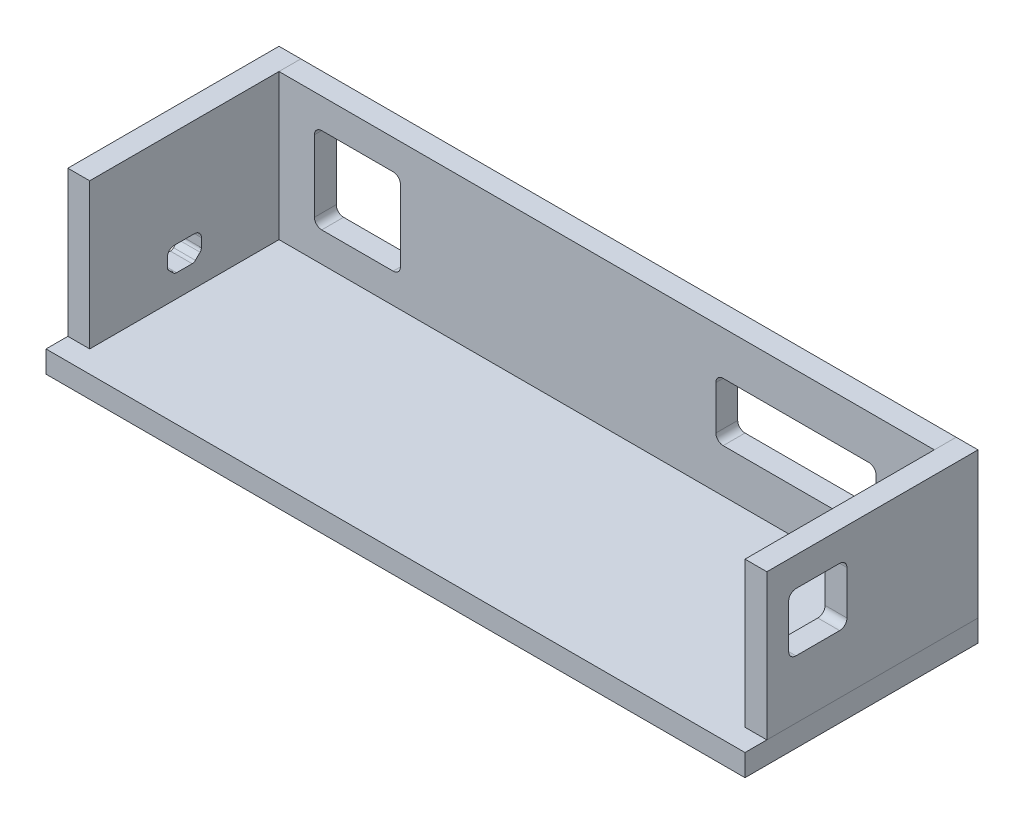
SolidWorks part; units mm, degrees
ref_plane "Front Plane" through (0, 0, 0) normal (0, 0, 1) x (1, 0, 0)
ref_plane "Top Plane" through (0, 0, 0) normal (0, 1, 0) x (1, 0, 0)
ref_plane "Right Plane" through (0, 0, 0) normal (1, 0, 0) x (0, 0, -1)
sketch "Sketch1" plane through (0, 0, 0) normal (0, 1, 0) x (1, 0, 0)
  line L1 (-304.8, 101.6) -> (304.8, 101.6)
  line L2 (-304.8, 101.6) -> (-304.8, -101.6)
  line L3 (-304.8, -101.6) -> (304.8, -101.6)
  line L4 (304.8, 101.6) -> (304.8, -101.6)
  line L5 (-304.8, 101.6) -> (304.8, -101.6) construction
  line L6 (-304.8, -101.6) -> (304.8, 101.6) construction
  point P0 (0, 0)
  dimension "D1" = 609.6
  dimension "D2" = 203.2
extrude "Boss-Extrude1" add sketch "Sketch1" along normal blind 19.05
sketch "Sketch2" plane through (0, 19.05, 0) normal (0, 1, 0) x (1, 0, 0)
  line L0 (-304.8, -101.6) -> (304.8, -101.6) construction
  line L1 (-304.8, 101.6) -> (-285.75, 101.6)
  line L2 (-304.8, 101.6) -> (-304.8, -101.6)
  line L3 (-304.8, -101.6) -> (-285.75, -101.6)
  line L4 (-285.75, 101.6) -> (-285.75, -101.6)
  line L5 (304.8, 101.6) -> (-304.8, 101.6) construction
  line L6 (304.8, -101.6) -> (285.75, -101.6)
  line L7 (304.8, -101.6) -> (304.8, 101.6)
  line L8 (304.8, 101.6) -> (285.75, 101.6)
  line L9 (285.75, -101.6) -> (285.75, 101.6)
  line L11 (-285.75, 101.6) -> (285.75, 101.6)
  line L12 (-285.75, 101.6) -> (-285.75, 82.55)
  line L13 (-285.75, 82.55) -> (285.75, 82.55)
  line L14 (285.75, 101.6) -> (285.75, 82.55)
  line M7 (304.8, -101.6) -> (304.8, 101.6)
  line M8 (304.8, 101.6) -> (-304.8, 101.6)
  line M9 (-304.8, 101.6) -> (-304.8, -101.6)
  line M10 (-304.8, -101.6) -> (304.8, -101.6)
  dimension "D1" = 19.05
  dimension "D2" = 19.05
  dimension "D3" = 19.05
extrude "Boss-Extrude2" add sketch "Sketch2" along normal blind 127 separate body contours L4 M8 M9 M10 | L9 M10 M7 M8 region at (-295.275, 19.05, 0) region at (295.275, 19.05, 0)
extrude "Boss-Extrude3" add sketch "Sketch2<3>" along normal up to surface (127 mm away) separate body contours L4 L13 L9 M8 region at (0, 19.05, -92.075) up to face at (-295.275, 146.05, 0)
sketch "Sketch2<3>" plane through (0, 19.05, 0) normal (0, 1, 0) x (1, 0, 0) same geometry as "Sketch2"
sketch "Sketch4" plane through (0, 19.05, 0) normal (0, 1, 0) x (1, 0, 0)
  line L0 (285.75, -101.6) -> (285.75, 101.6) construction
  line L1 (-285.75, -101.6) -> (285.75, -101.6)
  line L2 (-285.75, -101.6) -> (-285.75, -82.55)
  line L3 (-285.75, -82.55) -> (285.75, -82.55)
  line L4 (285.75, -101.6) -> (285.75, -82.55)
  dimension "D1" = 19.05
extrude "Boss-Extrude5" add sketch "Sketch4" along normal blind 6.35 separate body
sketch "Sketch5" plane through (-304.8, 0, -304.8) normal (1, 0, 0) x (0, 0, -1)
  line L0 (-203.2, 82.55) -> (-406.4, 82.55) construction
  line L1 (-203.2, 146.05) -> (-203.2, 19.05) construction
  line L2 (-406.4, 146.05) -> (-406.4, 19.05) construction
  line L3 (-304.8, 82.55) -> (-304.8, 19.05) construction
  line L4 (-203.2, 19.05) -> (-406.4, 19.05) construction
  line L26 (-295.1743, 39.8975) -> (-291.0923, 43.9795)
  line L27 (-289.9361, 46.7691) -> (-289.9361, 54.4059)
  line L28 (-295.9636, 60.4385) -> (-313.5841, 60.4385)
  line L29 (-319.6321, 54.3905) -> (-319.6321, 46.8124)
  line L30 (-318.4465, 43.95) -> (-314.4246, 39.9281)
  line L31 (-311.5622, 38.7425) -> (-309.7841, 38.7425)
  line L32 (-309.7841, 38.7425) -> (-299.7841, 38.7425)
  line L33 (-299.7841, 38.7425) -> (-297.9644, 38.7425)
  spline S18 degree 3 poles (-291.0923, 43.9795) (-291.0033, 44.0735) (-290.9158, 44.1689) (-290.7535, 44.3694) (-290.6774, 44.4737) (-290.4636, 44.7979) (-290.3426, 45.0263) (-290.1465, 45.4989) (-290.0705, 45.7454) (-289.9923, 46.1261) (-289.9724, 46.2537) (-289.9454, 46.5104) (-289.9398, 46.6397) (-289.9361, 46.7691) knots 0 0 0 0 0.125 0.125 0.25 0.25 0.5 0.5 0.75 0.75 0.875 0.875 1 1 1 1
  spline S19 degree 3 poles (-289.9361, 54.4059) (-289.9381, 54.6045) (-289.9467, 54.8019) (-289.9861, 55.1929) (-290.0151, 55.3868) (-290.0921, 55.7711) (-290.1401, 55.9616) (-290.2552, 56.3393) (-290.3228, 56.5272) (-290.5499, 57.0745) (-290.7344, 57.4205) (-291.1705, 58.0741) (-291.4251, 58.3841) (-291.9809, 58.9409) (-292.2833, 59.191) (-292.7753, 59.5217) (-292.9465, 59.6247) (-293.2946, 59.8114) (-293.4723, 59.8957) (-294.0155, 60.1225) (-294.3917, 60.2394) (-294.9766, 60.3577) (-295.1726, 60.3872) (-295.5666, 60.4274) (-295.7648, 60.4358) (-295.9636, 60.4385) knots 0 0 0 0 0.0625 0.0625 0.125 0.125 0.1875 0.1875 0.25 0.25 0.375 0.375 0.5 0.5 0.625 0.625 0.6875 0.6875 0.75 0.75 0.875 0.875 0.9375 0.9375 1 1 1 1
  spline S20 degree 3 poles (-313.5841, 60.4385) (-313.9834, 60.4385) (-314.376, 60.3998) (-314.9552, 60.2847) (-315.1466, 60.2368) (-315.5262, 60.1217) (-315.7149, 60.0541) (-316.2641, 59.827) (-316.6115, 59.6419) (-317.2686, 59.2036) (-317.5795, 58.9479) (-318.1377, 58.3905) (-318.3886, 58.0866) (-318.7204, 57.5913) (-318.8233, 57.4195) (-319.0098, 57.0704) (-319.094, 56.8921) (-319.3205, 56.3466) (-319.4373, 55.9666) (-319.5935, 55.185) (-319.6321, 54.7899) (-319.6321, 54.3905) knots 0 0 0 0 0.125 0.125 0.1875 0.1875 0.25 0.25 0.375 0.375 0.5 0.5 0.625 0.625 0.6875 0.6875 0.75 0.75 0.875 0.875 1 1 1 1
  spline S21 degree 3 poles (-319.6321, 46.8124) (-319.6321, 46.5457) (-319.6061, 46.2818) (-319.5017, 45.7593) (-319.4244, 45.5064) (-319.2237, 45.0204) (-319.0984, 44.7849) (-318.8033, 44.3432) (-318.6351, 44.1386) (-318.4465, 43.95) knots 0 0 0 0 0.25 0.25 0.5 0.5 0.75 0.75 1 1 1 1
  spline S22 degree 3 poles (-314.4246, 39.9281) (-314.236, 39.7395) (-314.0309, 39.5713) (-313.5877, 39.2757) (-313.3542, 39.1515) (-312.8686, 38.9498) (-312.6135, 38.8719) (-312.0925, 38.7682) (-311.8289, 38.7425) (-311.5622, 38.7425) knots 0 0 0 0 0.25 0.25 0.5 0.5 0.75 0.75 1 1 1 1
  spline S23 degree 3 poles (-297.9644, 38.7425) (-297.8349, 38.746) (-297.7057, 38.7516) (-297.4491, 38.7786) (-297.3215, 38.7985) (-296.9411, 38.8766) (-296.6941, 38.9525) (-296.2213, 39.1481) (-295.9932, 39.2686) (-295.6687, 39.4825) (-295.5644, 39.5587) (-295.3638, 39.7211) (-295.2684, 39.8086) (-295.1743, 39.8975) knots 0 0 0 0 0.125 0.125 0.25 0.25 0.5 0.5 0.75 0.75 0.875 0.875 1 1 1 1
  point P11 (-304.7739, 60.4385)
extrude "Cut-Extrude1" cut sketch "Sketch5" along normal up to surface (19.05 mm away) up to face at (-285.75, 82.55, 0)
sketch "Sketch6" plane through (0, 0, -82.55) normal (0, 0, 1) x (1, 0, 0)
  line L0 (-285.75, 146.05) -> (285.75, 146.05) construction
  line L1 (95.25, 107.95) -> (234.95, 107.95)
  line L2 (95.25, 107.95) -> (95.25, 57.15)
  line L3 (95.25, 57.15) -> (234.95, 57.15)
  line L4 (234.95, 107.95) -> (234.95, 57.15)
  line L5 (95.25, 107.95) -> (234.95, 57.15) construction
  line L6 (95.25, 57.15) -> (234.95, 107.95) construction
  line L7 (285.75, 146.05) -> (285.75, 19.05) construction
  point P0 (165.1, 82.55)
  dimension "D1" = 63.5
  dimension "D2" = 50.8
  dimension "D3" = 139.7
  dimension "D4" = 50.8
extrude "Cut-Extrude2" cut sketch "Sketch6" against normal through all
sketch "Sketch9" plane through (0, 0, -82.55) normal (0, 0, 1) x (1, 0, 0)
  line L0 (-285.75, 19.05) -> (285.75, 19.05) construction
  line L1 (-254.8532, 120.05) -> (-179.8532, 120.05)
  line L2 (-254.8532, 120.05) -> (-254.8532, 45.05)
  line L3 (-254.8532, 45.05) -> (-179.8532, 45.05)
  line L4 (-179.8532, 120.05) -> (-179.8532, 45.05)
  line L5 (-254.8532, 120.05) -> (-179.8532, 45.05) construction
  line L6 (-254.8532, 45.05) -> (-179.8532, 120.05) construction
  point P0 (-217.3532, 82.55)
  dimension "D1" = 75
  dimension "D2" = 75
  dimension "D3" = 63.5
extrude "Cut-Extrude3" cut sketch "Sketch9" against normal through all
sketch "Sketch10" plane through (285.75, 0, 0) normal (-1, 0, 0) x (0, 0, 1)
  line L0 (101.6, 146.05) -> (-101.6, 146.05) construction
  line L1 (12.7, 120.65) -> (63.5, 120.65)
  line L2 (12.7, 120.65) -> (12.7, 69.85)
  line L3 (12.7, 69.85) -> (63.5, 69.85)
  line L4 (63.5, 120.65) -> (63.5, 69.85)
  line L5 (12.7, 120.65) -> (63.5, 69.85) construction
  line L6 (12.7, 69.85) -> (63.5, 120.65) construction
  line L7 (101.6, 146.05) -> (101.6, 19.05) construction
  point P0 (38.1, 95.25)
  dimension "D1" = 50.8
  dimension "D2" = 50.8
  dimension "D3" = 50.8
  dimension "D5" = 38.1
extrude "Cut-Extrude4" cut sketch "Sketch10" against normal through all
fillet "Fillet1" radius 6.35 8 edges at (234.95, 107.95, -92.075) (234.95, 57.15, -92.075) (95.25, 57.15, -92.075) (95.25, 107.95, -92.075) (-254.8532, 45.05, -92.075) (-179.8532, 45.05, -92.075) (-254.8532, 120.05, -92.075) (-179.8532, 120.05, -92.075)
fillet "Fillet2" radius 6.35 4 edges at (295.275, 120.65, 63.5) (295.275, 69.85, 63.5) (295.275, 69.85, 12.7) (295.275, 120.65, 12.7)
sketch "Sketch11" plane through (-304.8, 0, 0) normal (-1, 0, 0) x (0, 0, 1)
  line L0 (-101.6, 146.05) -> (101.6, 146.05) construction
  line L1 (101.6, 19.05) -> (82.55, 19.05)
  line L2 (101.6, 19.05) -> (101.6, 146.05)
  line L3 (101.6, 146.05) -> (82.55, 146.05)
  line L4 (82.55, 19.05) -> (82.55, 146.05)
  dimension "D1" = 19.05
extrude "Cut-Extrude5" cut sketch "Sketch11" against normal through all
